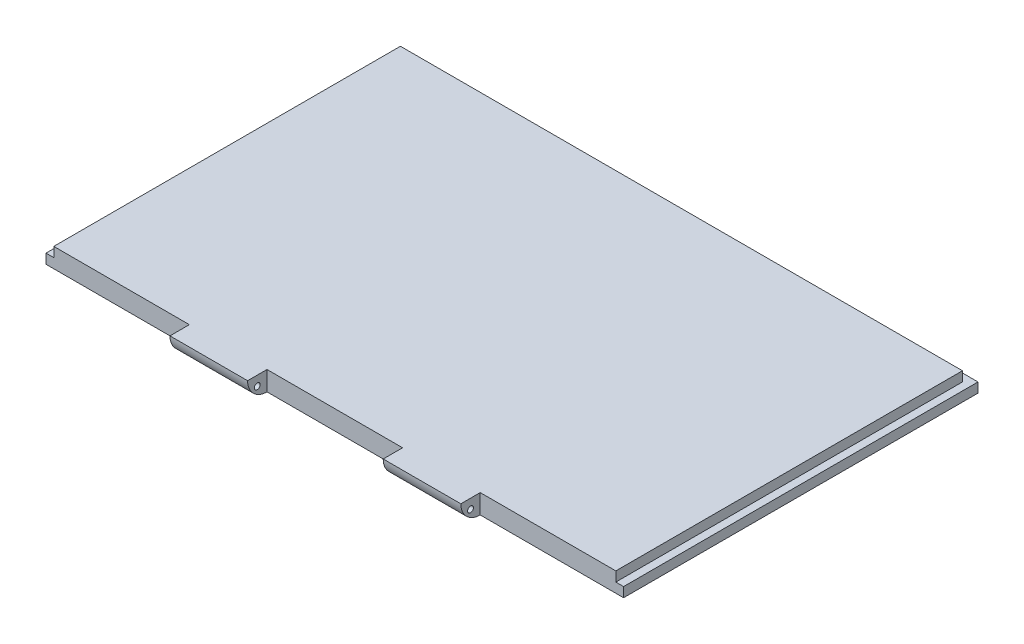
SolidWorks part; units mm, degrees
ref_plane "Front Plane" through (0, 0, 0) normal (0, 0, 1) x (1, 0, 0)
ref_plane "Top Plane" through (0, 0, 0) normal (0, 1, 0) x (1, 0, 0)
ref_plane "Right Plane" through (0, 0, 0) normal (1, 0, 0) x (0, 0, -1)
sketch "Sketch1" plane through (0, 0, 0) normal (0, 1, 0) x (1, 0, 0)
  line L0 (-59.4022, -153.4028) -> (29.3378, -153.4028)
  line L2 (308.4178, -153.4028) -> (308.4178, 73.4472)
  line L3 (308.4178, 73.4472) -> (-59.4022, 73.4472)
  line L4 (-59.4022, -153.4028) -> (-59.4022, 73.4472)
  line L5 (308.4178, -153.4028) -> (-59.4022, 73.4472) construction
  line L6 (308.4178, 73.4472) -> (-59.4022, -153.4028) construction
  line L7 (29.3378, -153.4028) -> (29.3378, -166.1028)
  line L8 (29.3378, -166.1028) -> (80.1378, -166.1028)
  line L9 (80.1378, -166.1028) -> (80.1378, -153.4028)
  line L10 (80.1378, -153.4028) -> (168.8778, -153.4028)
  line L11 (168.8778, -153.4028) -> (168.8778, -166.1028)
  line L12 (168.8778, -166.1028) -> (219.6778, -166.1028)
  line L13 (219.6778, -153.4028) -> (219.6778, -166.1028) construction
  line L14 (219.6778, -166.1028) -> (219.6778, -153.4028)
  line L15 (219.6778, -153.4028) -> (308.4178, -153.4028)
  point P0 (124.5078, -39.9778)
extrude "Boss-Extrude1" add sketch "Sketch1" along normal blind 6.35
sketch "Sketch2" plane through (0, 0, 0) normal (0, -1, 0) x (1, 0, 0)
  line L0 (29.3378, 153.4028) -> (29.3378, 166.1028)
  line L2 (29.3378, 153.4028) -> (29.3378, 166.1028) construction
  line L3 (29.3378, 166.1028) -> (80.1378, 166.1028)
  line L4 (80.1378, 166.1028) -> (80.1378, 153.4028)
  line L5 (80.1378, 166.1028) -> (80.1378, 153.4028) construction
  line L6 (80.1378, 153.4028) -> (168.8778, 153.4028)
  line L7 (168.8778, 153.4028) -> (168.8778, 166.1028) construction
  line L8 (168.8778, 153.4028) -> (168.8778, 166.1028)
  line L9 (168.8778, 166.1028) -> (219.6778, 166.1028)
  line L10 (219.6778, 166.1028) -> (219.6778, 153.4028)
  line L11 (219.6778, 166.1028) -> (219.6778, 153.4028) construction
  line L12 (219.6778, 153.4028) -> (313.4978, 153.4028)
  line L13 (313.4978, -78.5272) -> (313.4978, 166.1028) construction
  line L14 (313.4978, 153.4028) -> (313.4978, -78.5272)
  line L15 (313.4978, -78.5272) -> (-64.4822, -78.5272)
  line L16 (-64.4822, -78.5272) -> (-64.4822, 153.4028)
  line L17 (-64.4822, 166.1028) -> (-64.4822, -78.5272) construction
  line L18 (-64.4822, 153.4028) -> (29.3378, 153.4028)
  point P32 (0, 0)
  point P33 (0, 0)
  point P34 (0, 0)
  point P35 (0, 0)
  point P36 (0, 0)
extrude "Boss-Extrude2" add sketch "Sketch2" along normal blind 6.35
sketch "Sketch3" plane through (29.3378, 0, 0) normal (-1, 0, 0) x (0, 0, 1)
  circle A0 centre (159.7528, 0) radius 1.905
extrude "Cut-Extrude1" cut sketch "Sketch3" against normal up to surface (190.34 mm away) up to face at (219.6778, 0, 159.7528)
fillet "Fillet2" radius 12.7 2 edges at (54.7378, -6.35, 166.1028) (194.2778, -6.35, 166.1028)
